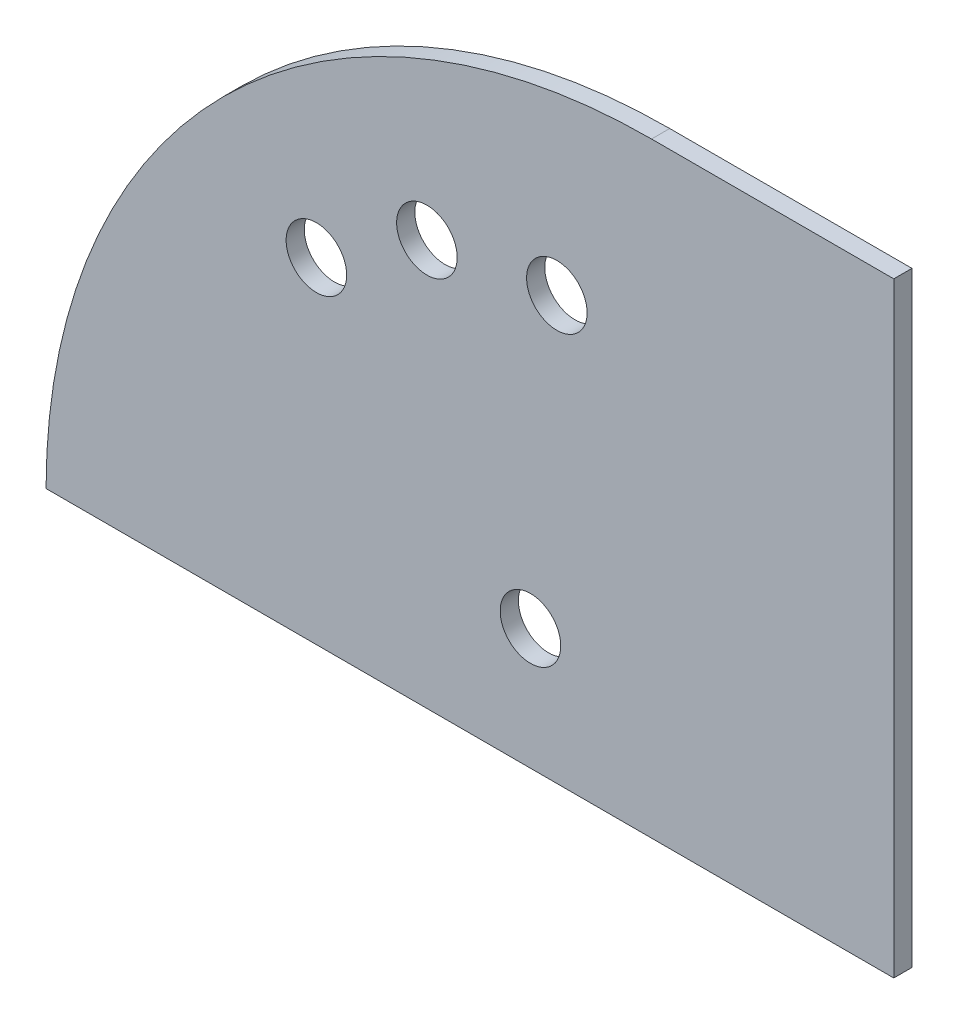
SolidWorks part; units mm, degrees
ref_plane "Plano frontal" through (0, 0, 0) normal (0, 0, 1) x (1, 0, 0)
ref_plane "Plano superior" through (0, 0, 0) normal (0, 1, 0) x (1, 0, 0)
ref_plane "Plano direito" through (0, 0, 0) normal (1, 0, 0) x (0, 0, -1)
sketch "Esboço1" plane through (0, 0, 0) normal (0, 0, 1) x (1, 0, 0)
  line L0 (0, 0) -> (-100, 0)
  line L1 (0, 0) -> (40, 0)
  line L2 (0, 0) -> (0, 100) construction
  line L3 (0, 100) -> (40, 100)
  line L4 (40, 0) -> (40, 100)
  line L5 (0, 0) -> (-70.7107, 70.7107) construction
  line L7 (-20, 20) -> (-55.3553, 55.3553) construction
  arc A0 (-100, 0) -> (0, 100) centre (0, 0) cw
  circle A1 centre (-20, 20) radius 5
  circle A2 centre (-55.3553, 55.3553) radius 5
  circle A5 centre (-37.101, 66.9846) radius 5
  circle A6 centre (-15.6422, 69.8097) radius 5
  dimension "D3" = 10
  dimension "D4" = 20
  dimension "D5" = 50
  dimension "D1" = 40
  dimension "D2" = 100
  dimension "D9" = 50
  dimension "D8" = 3
base flange "Flange-base1" sketch "Esboço1" thickness 3 reverse thickness direction no parameters "D1"=0.7366
sketch "Curva-Linhas1" [suppressed] plane through (0, 0, 0) normal (0, 1, 0) x (1, 0, 0)
sketch "Caixa delimitadora1" [suppressed] plane through (0, 0, 0) normal (0, 1, 0) x (1, 0, 0)
sheet metal parameters "Chapa metálica1" thickness 3 parameters "D1"=0.7366
flat pattern "Padrão-Plano1" [suppressed]
sketch "Curva-Linhas2" plane through (0, 0, 0) normal (0, 1, 0) x (1, 0, 0)
sketch3d "Caixa delimitadora2" [suppressed]
  line L0 (-100, 0, 0) -> (40, 0, 0) construction
  line L1 (-100, 100, 0) -> (40, 100, 0) construction
  line L2 (-100, 0, 0) -> (-100, 100, 0) construction
  line L3 (40, 0, 0) -> (40, 100, 0) construction
